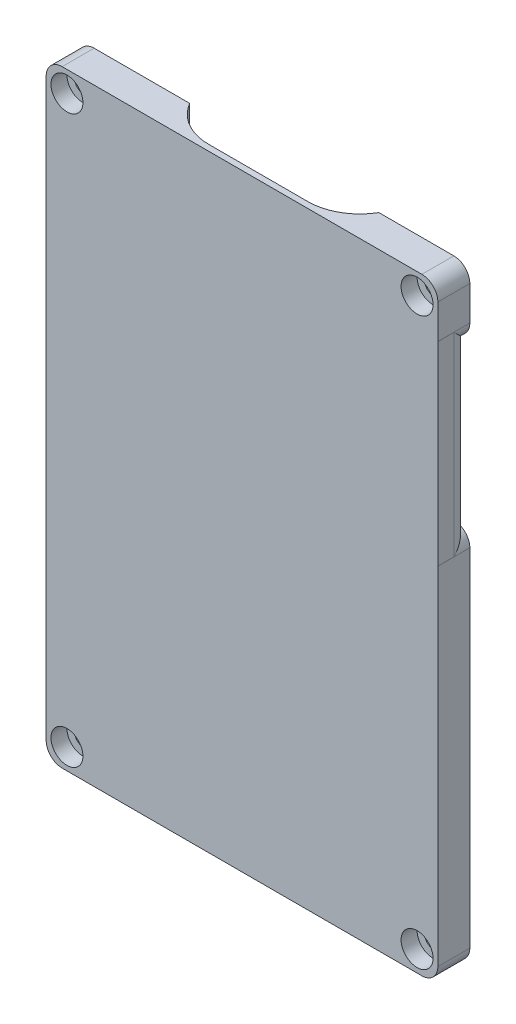
SolidWorks part; units mm, degrees
other "标注1"
sketch "草图6" plane through (-121.7901, 77.7286, -9) normal (-0.0529, 0.1135, -0.9921) x (-0.9984, 0.0112, 0.0545)
ref_plane "前视基准面" through (0, 0, 0) normal (0, 0, 1) x (1, 0, 0)
ref_plane "上视基准面" through (0, 0, 0) normal (0, 1, 0) x (1, 0, 0)
ref_plane "右视基准面" through (0, 0, 0) normal (1, 0, 0) x (0, 0, -1)
sketch "草图1" plane through (0, 0, 0) normal (0, 0, 1) x (1, 0, 0)
  line L1 (-97.7901, 77.7286) -> (-122.2901, 77.7286)
  line L2 (-97.7901, 77.7286) -> (-97.7901, 39.7286)
  line L3 (-97.7901, 39.7286) -> (-122.2901, 39.7286)
  line L4 (-122.2901, 77.7286) -> (-122.2901, 39.7286)
  dimension "D1" = 24.5
  dimension "D2" = 38
extrude "凸台-拉伸1" add sketch "草图1" along normal blind 2
sketch "草图9" plane through (0, 0, 2) normal (0, 0, 1) x (1, 0, 0)
  line L1 (-97.7901, 39.7286) -> (-97.7901, 77.7286) construction
  line L5 (-122.2901, 39.7286) -> (-97.7901, 39.7286) construction
  line L6 (-122.2901, 77.7286) -> (-122.2901, 39.7286) construction
  line L7 (-97.7901, 77.7286) -> (-122.2901, 77.7286) construction
  circle A0 centre (-99.0901, 76.4286) radius 1
  circle A1 centre (-99.0901, 41.0286) radius 1
  circle A2 centre (-120.9901, 41.0286) radius 1
  circle A3 centre (-120.9901, 76.4286) radius 1
  dimension "D1" = 1.3
  dimension "D2" = 1.3
  dimension "D4" = 1.3
  dimension "D5" = 1.3
extrude "切除-拉伸3" cut sketch "草图9" against normal blind 1
sketch "草图10" plane through (0, 0, 1) normal (0, 0, 1) x (1, 0, 0)
  circle A0 centre (-120.9901, 41.0286) radius 0.5
  circle A1 centre (-99.0901, 41.0286) radius 0.5
  circle A2 centre (-99.0901, 76.4286) radius 0.5
  circle A3 centre (-120.9901, 76.4286) radius 0.5
  circle A5 centre (-120.9901, 76.4286) radius 1 construction
  circle A6 centre (-99.0901, 76.4286) radius 1 construction
  circle A7 centre (-120.9901, 41.0286) radius 1 construction
  circle A8 centre (-99.0901, 41.0286) radius 1 construction
  dimension "D1" = 1
extrude "切除-拉伸4" cut sketch "草图10" against normal up to next
fillet "圆角1" radius 1 4 edges at (-97.7901, 77.7286, 1) (-97.7901, 39.7286, 1) (-122.2901, 39.7286, 1) (-122.2901, 77.7286, 1)
sketch "草图11" plane through (0, 0, 0) normal (0, 0, -1) x (-1, 0, 0)
  line L0 (98.7901, 77.7286) -> (121.2901, 77.7286) construction
  line L1 (105.3271, 67.0786) -> (111.0901, 67.0786)
  line L2 (105.3271, 67.0786) -> (105.3271, 64.4229)
  line L3 (105.3271, 64.4229) -> (111.0901, 64.4229)
  line L4 (111.0901, 67.0786) -> (111.0901, 64.4229)
  line L5 (97.7901, 40.7286) -> (97.7901, 76.7286) construction
  dimension "D1" = 10.65
  dimension "D2" = 13.3
extrude "凸台-拉伸2" add sketch "草图11" along normal blind 3
sketch "草图12" plane through (0, 0, 0) normal (0, 0, -1) x (-1, 0, 0)
  line L1 (106.6363, 50.5248) -> (114.6363, 50.5248)
  line L2 (106.6363, 50.5248) -> (106.6363, 49.0286)
  line L3 (106.6363, 49.0286) -> (114.6363, 49.0286)
  line L4 (114.6363, 50.5248) -> (114.6363, 49.0286)
  line L5 (98.7901, 77.7286) -> (121.2901, 77.7286) construction
  dimension "D1" = 28.7
  dimension "D2" = 8
extrude "凸台-拉伸3" add sketch "草图12" along normal blind 2.2
sketch "草图14" plane through (-122.2901, 0, 0) normal (-1, 0, 0) x (0, 0, 1)
  line L1 (0, 75.2294) -> (2, 75.2294)
  line L2 (0, 75.2294) -> (0, 60.2104)
  line L3 (0, 60.2104) -> (2, 60.2104)
  line L4 (2, 75.2294) -> (2, 60.2104)
  line L6 (2, 76.7286) -> (2, 40.7286) construction
extrude "切除-拉伸6" cut sketch "草图14" against normal blind 0.0001
fillet "圆角3" radius 2 1 edges at (-122.29, 67.7199, 0)
sketch "草图16" plane through (0, 77.7286, 0) normal (0, 1, 0) x (1, 0, 0)
  line L0 (-112.4951, 1.625) -> (-106.2951, 1.625) construction
  line L2 (-112.4951, 4.875) -> (-106.2951, 4.875)
  line L3 (-112.4951, -1.625) -> (-106.2951, -1.625)
  line L4 (-106.2951, 4.875) -> (-112.4951, 4.875) construction
  arc A0 (-112.4951, 4.875) -> (-112.4951, -1.625) centre (-112.4951, 1.625) ccw
  arc A1 (-106.2951, -1.625) -> (-106.2951, 4.875) centre (-106.2951, 1.625) ccw
  arc A4 (-103.4805, 0) -> (-106.2951, 4.875) centre (-106.2951, 1.625) ccw construction
  arc A5 (-112.4951, 4.875) -> (-115.3097, 0) centre (-112.4951, 1.625) ccw construction
  point P4 (-109.3951, 1.625)
extrude "切除-拉伸7" cut sketch "草图16" against normal blind 3.7
sketch "草图17" plane through (-97.7901, 0, 0) normal (1, 0, 0) x (0, 0, -1)
  line L0 (-2, 40.7286) -> (-2, 76.7286) construction
  line L1 (-2, 73.6018) -> (0, 73.6018)
  line L2 (-2, 73.6018) -> (-2, 63.4039)
  line L3 (-2, 63.4039) -> (0, 63.4039)
  line L4 (0, 73.6018) -> (0, 63.4039)
  line L5 (0, 40.7286) -> (0, 76.7286) construction
extrude "切除-拉伸8" cut sketch "草图17" against normal blind 0.0001
fillet "圆角4" radius 1 1 edges at (-97.7902, 68.5028, 0)
fillet "圆角7" radius 1 2 edges at (-122.2901, 60.2104, 1) (-122.2901, 75.2294, 1)
fillet "圆角9" radius 0.99 2 edges at (-97.7901, 63.4039, 1) (-97.7901, 73.6018, 1)
